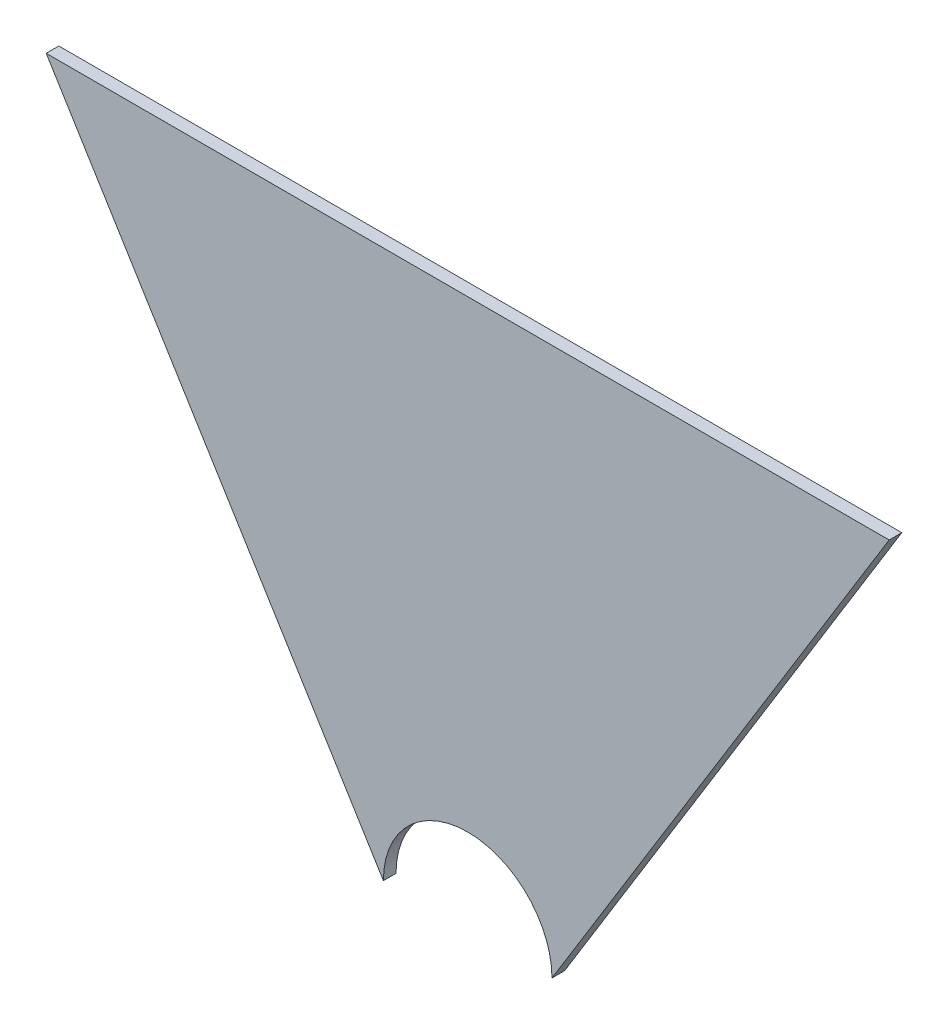
SolidWorks part; units mm, degrees
ref_plane "Front Plane" through (0, 0, 0) normal (0, 0, 1) x (1, 0, 0)
ref_plane "Top Plane" through (0, 0, 0) normal (0, 1, 0) x (1, 0, 0)
ref_plane "Right Plane" through (0, 0, 0) normal (1, 0, 0) x (0, 0, -1)
sketch "Sketch1" plane through (0, 0, 0) normal (0, 0, 1) x (1, 0, 0)
  line L0 (0, 0) -> (200, 0)
  line L2 (80, -130) -> (0, 0)
  line L3 (120, -130) -> (50.5312, -130) construction
  line L4 (200, 0) -> (120, -130)
  line L5 (100, -130) -> (100, 31.9558) construction
  arc A0 (120, -130) -> (80, -130) centre (100, -130) ccw
  point P6 (100, 0)
  dimension "D1" = 20
  dimension "D2" = 130
  dimension "D3" = 200
base flange "Base-Flange1" sketch "Sketch1" thickness 3 reverse thickness direction no parameters "D1"=0.7366
sketch "Bend-Lines1" [suppressed] plane through (0, 0, 0) normal (0, 1, 0) x (1, 0, 0)
sketch "Bounding-Box1" [suppressed] plane through (0, 0, 0) normal (0, 1, 0) x (1, 0, 0)
sheet metal parameters "Sheet-Metal1" thickness 3 parameters "D1"=0.7366
flat pattern "Flat-Pattern1" [suppressed]
sketch "Bend-Lines2" plane through (0, 0, 0) normal (0, 1, 0) x (1, 0, 0)
sketch3d "Bounding-Box2" [suppressed]
  line L0 (-100, 0, 0) -> (100, 0, 0) construction
  line L1 (-100, 130, 0) -> (100, 130, 0) construction
  line L2 (-100, 0, 0) -> (-100, 130, 0) construction
  line L3 (100, 0, 0) -> (100, 130, 0) construction
